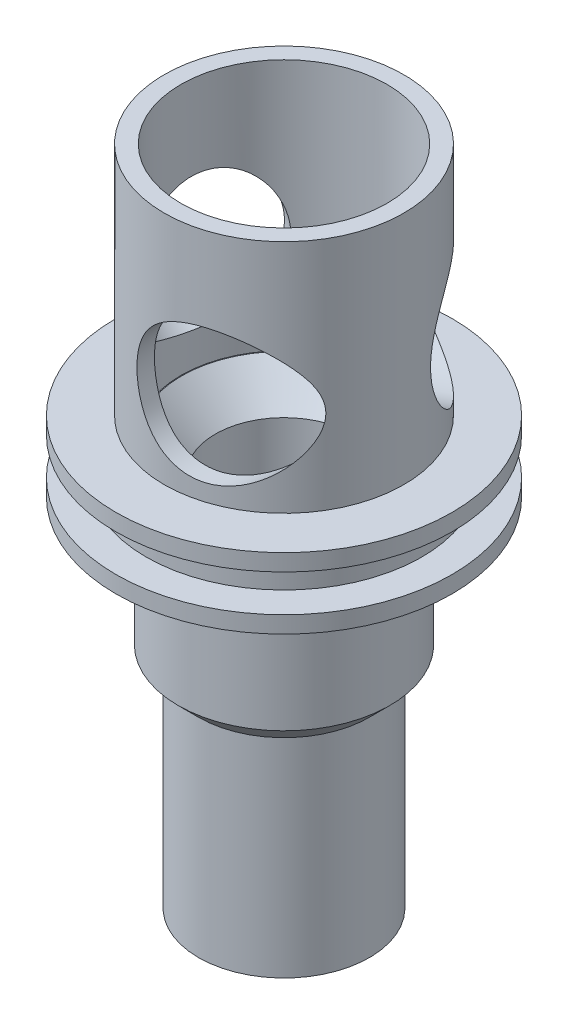
SolidWorks part; units mm, degrees
ref_plane "Front Plane" through (0, 0, 0) normal (0, 0, 1) x (1, 0, 0)
ref_plane "Top Plane" through (0, 0, 0) normal (0, 1, 0) x (1, 0, 0)
ref_plane "Right Plane" through (0, 0, 0) normal (1, 0, 0) x (0, 0, -1)
ref_axis "Centerline" through (0, 55, 0) along (0, -1, 0)
sketch "Sketch2" plane through (0, 0, 0) normal (0, 1, 0) x (1, 0, 0)
  circle A0 centre (0, 0) radius 12.7
  dimension "D1" = 25.4
extrude "Solid Cylinder" add sketch "Sketch2" along normal blind 50.038
sketch "Sketch3" plane through (0, 50.038, 0) normal (0, 1, 0) x (1, 0, 0)
  circle A0 centre (0, 0) radius 5.1918
  dimension "D1" = 10.3835
extrude "All Through Hole" cut sketch "Sketch3" against normal up to next
sketch "Sketch4" plane through (0, 50.038, 0) normal (0, 1, 0) x (1, 0, 0)
  circle A0 centre (0, 0) radius 7.7902
  dimension "D1" = 15.5804
extrude "Swirl Chamber" cut sketch "Sketch4" against normal blind 19.05
sketch "Sketch5" plane through (0, 50.038, 0) normal (0, 1, 0) x (1, 0, 0)
  circle A0 centre (0, 0) radius 9.0602
  circle A1 centre (0, 0) radius 12.7
  circle A2 centre (0, 0) radius 12.7 construction
  circle A3 centre (0, 0) radius 7.7902 construction
  circle A4 centre (0, 0) radius 7.7902 construction
  dimension "D1" = 1.27
extrude "Top Outer cut" cut sketch "Sketch5" against normal blind 17.78
sketch "Sketch8" plane through (0, 0, 0) normal (0, 0, 1) x (1, 0, 0)
  line L0 (12.7, 0) -> (12.7, 32.258) construction
  line L1 (12.7, 30.988) -> (10.414, 30.988)
  line L2 (12.7, 30.988) -> (12.7, 28.194)
  line L3 (12.7, 28.194) -> (10.414, 28.194)
  line L4 (10.414, 30.988) -> (10.414, 28.194)
  line L5 (12.7, 32.258) -> (-12.7, 32.258) construction
  dimension "D1" = 2.794
  dimension "D2" = 2.286
  dimension "D3" = 1.27
revolve "O Ring Cut" cut sketch "Sketch8" angle 360 about axis through (0, 55, 0) along (0, -1, 0)
sketch "Sketch9" plane through (0, 0, 0) normal (0, 0, 1) x (1, 0, 0)
  line L0 (12.7, 28.194) -> (-12.7, 28.194) construction
  line L1 (12.7, 0) -> (8.001, 0)
  line L2 (12.7, 0) -> (12.7, 26.924)
  line L3 (12.7, 26.924) -> (8.001, 26.924)
  line L4 (8.001, 0) -> (8.001, 26.924)
  dimension "D1" = 4.699
  dimension "D2" = 1.27
revolve "Base Support" cut sketch "Sketch9" angle 360 about axis through (0, 55, 0) along (0, -1, 0)
chamfer "Inner Chamfer" distance 2.54 angle 45 1 edges at (0, 30.988, 5.1918)
sketch "Sketch12" plane through (0, 0, 0) normal (0, 0, 1) x (1, 0, 0)
  line L0 (0, 50.038) -> (0, 0) construction
  line L1 (7.7902, 50.038) -> (7.7902, 0) construction
  line L3 (7.7902, 50.038) -> (-7.7902, 50.038) construction
  line L4 (0, 0) -> (7.7902, 0) construction
  line L5 (0, 50.038) -> (7.7902, 50.038) construction
  line L6 (2.7102, 43.688) -> (2.7102, 50.038) construction
  line L8 (7.7902, 50.038) -> (-7.7902, 50.038) construction
  line L9 (7.7902, 32.258) -> (0, 32.258) construction
  line L10 (9.0602, 32.258) -> (-9.0602, 32.258) construction
  line L11 (2.7102, 33.528) -> (2.7102, 32.258) construction
  circle A0 centre (2.7102, 38.608) radius 5.08
  dimension "D1" = 10.16
  dimension "D2" = 1.27
extrude "Inlet Hole" cut sketch "Sketch12" along normal up to next
pattern_circular "Inlet Hole Pattern" count 3 over 360 about axis through (0, 55, 0) along (0, -1, 0) of "Inlet Hole"
sketch "Sketch13" plane through (0, 0, 0) normal (0, 0, 1) x (1, 0, 0)
  line L1 (-8.001, 26.924) -> (-8.001, 0) construction
  line L4 (-8.001, 0) -> (-8.001, 17.272)
  line L5 (-8.001, 0) -> (8.001, 0) construction
  line L7 (0, 46.5908) -> (0, 0) construction
  line L9 (-6.4618, 0) -> (-5.1918, 0) construction
  line L13 (-6.4618, 0) -> (-6.4618, 15.7328)
  line L14 (-6.4618, 15.7328) -> (-8.001, 17.272)
  line L17 (-8.001, 0) -> (-6.4618, 0)
  line L18 (-6.4618, 15.7328) -> (-8.001, 15.7328) construction
  dimension "D1" = 1.27
  dimension "D2" = 9.652
  dimension "D3" = 45
revolve "Outer Chamfer and Stem" cut sketch "Sketch13" angle 360 about L7
